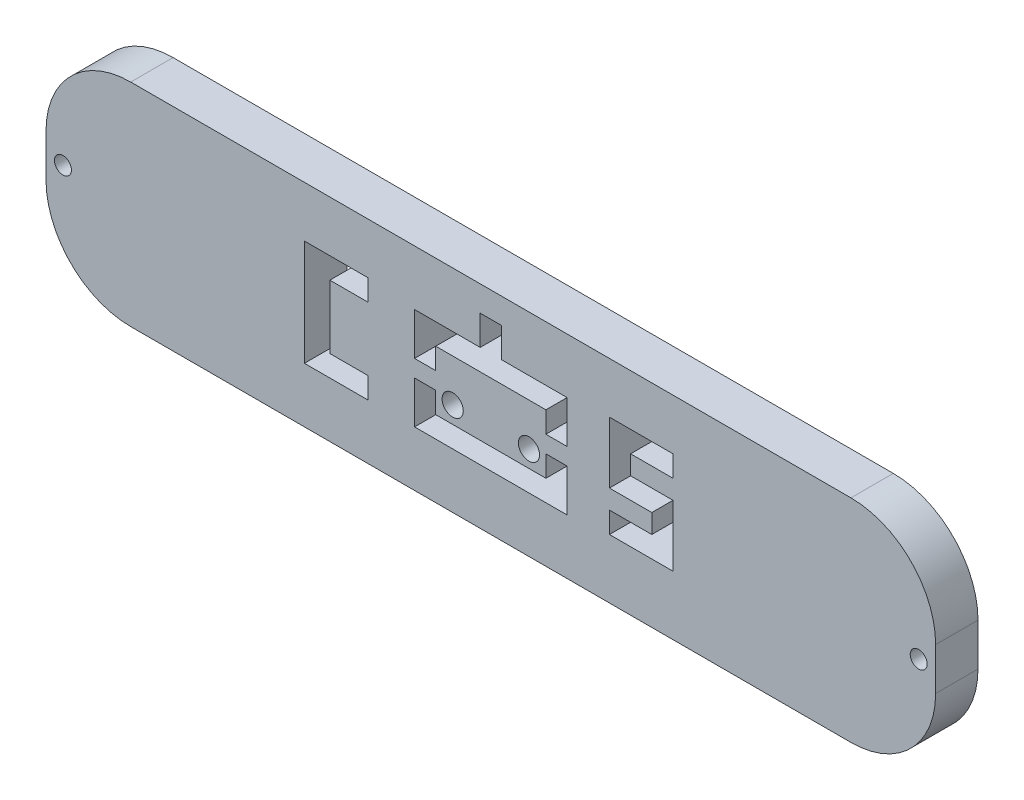
SolidWorks part; units mm, degrees
ref_plane "Alzado" through (0, 0, 0) normal (0, 0, 1) x (1, 0, 0)
ref_plane "Planta" through (0, 0, 0) normal (0, 1, 0) x (1, 0, 0)
ref_plane "Vista lateral" through (0, 0, 0) normal (1, 0, 0) x (0, 0, -1)
sketch "Croquis1" plane through (0, 0, 0) normal (0, 0, 1) x (1, 0, 0)
  line L0 (105, -50) -> (105, 0) construction
  line L1 (0, 0) -> (210, 0)
  line L2 (0, 0) -> (0, -50)
  line L3 (0, -50) -> (210, -50)
  line L4 (210, 0) -> (210, -50)
  line L5 (97.2718, -25) -> (112.9329, -25) construction
  line L6 (87, -13) -> (92, -13)
  line L7 (87, -13) -> (87, -23)
  line L8 (87, -23) -> (92, -23)
  line L9 (92, -13) -> (92, -23)
  line L10 (87, -13) -> (123, -13)
  line L11 (87, -13) -> (87, -18)
  line L12 (87, -18) -> (123, -18)
  line L13 (123, -13) -> (123, -18)
  line L14 (123, -13) -> (118, -13)
  line L15 (123, -13) -> (123, -23)
  line L16 (123, -23) -> (118, -23)
  line L17 (118, -13) -> (118, -23)
  line L18 (123, -27) -> (118, -27)
  line L19 (123, -37) -> (123, -27)
  line L20 (118, -37) -> (118, -27)
  line L21 (87, -37) -> (123, -37)
  line L22 (87, -32) -> (123, -32)
  line L23 (87, -37) -> (87, -27)
  line L24 (87, -27) -> (92, -27)
  line L25 (92, -37) -> (92, -27)
  line L27 (102.5, -6) -> (107.5, -6)
  line L28 (102.5, -6) -> (102.5, -18)
  line L29 (102.5, -18) -> (107.5, -18)
  line L30 (107.5, -6) -> (107.5, -18)
  line L31 (76, -12) -> (61, -12)
  line L32 (76, -12) -> (76, -17)
  line L33 (76, -17) -> (61, -17)
  line L34 (61, -12) -> (61, -17)
  line L35 (61, -12) -> (67, -12)
  line L36 (61, -12) -> (61, -37)
  line L37 (61, -37) -> (67, -37)
  line L38 (67, -12) -> (67, -37)
  line L39 (61, -37) -> (76, -37)
  line L40 (61, -37) -> (61, -32)
  line L41 (61, -32) -> (76, -32)
  line L42 (76, -37) -> (76, -32)
  line L43 (148, -12) -> (133, -12)
  line L44 (148, -12) -> (148, -17)
  line L45 (148, -17) -> (133, -17)
  line L46 (133, -12) -> (133, -17)
  line L47 (133, -12) -> (138, -12)
  line L48 (133, -12) -> (133, -26.5)
  line L49 (133, -26.5) -> (138, -26.5)
  line L50 (138, -12) -> (138, -26.5)
  line L51 (133, -26.5) -> (148, -26.5)
  line L52 (133, -26.5) -> (133, -21.5)
  line L53 (133, -21.5) -> (148, -21.5)
  line L54 (148, -26.5) -> (148, -21.5)
  line L55 (148, -21.5) -> (143, -21.5)
  line L56 (148, -21.5) -> (148, -31)
  line L57 (148, -31) -> (143, -31)
  line L58 (143, -21.5) -> (143, -31)
  line L59 (148, -31) -> (133, -31)
  line L60 (148, -31) -> (148, -36)
  line L61 (148, -36) -> (133, -36)
  line L62 (133, -31) -> (133, -36)
  circle A0 centre (4, -25) radius 2
  circle A1 centre (206, -25) radius 2
  circle A2 centre (96, -28) radius 2.5
  circle A3 centre (114, -28) radius 2.5
  dimension "D3" = 4
  dimension "D4" = 101
  dimension "D5" = 25
  dimension "D6" = 4
  dimension "D7" = 25
  dimension "D8" = 101
  dimension "D17" = 5
  dimension "D18" = 4
  dimension "D19" = 4
  dimension "D20" = 5
  dimension "D21" = 4
  dimension "D22" = 4
  dimension "D45" = 25
  dimension "D30" = 20
  dimension "D31" = 15
  dimension "D32" = 15
  dimension "D33" = 5
  dimension "D34" = 15
  dimension "D35" = 5
  dimension "D1" = 210
  dimension "D2" = 50
  dimension "D9" = 13
  dimension "D10" = 5
  dimension "D11" = 10
  dimension "D12" = 13
  dimension "D13" = 5
  dimension "D14" = 5
  dimension "D15" = 13
  dimension "D16" = 10
  dimension "D23" = 2.5
  dimension "D24" = 2.5
  dimension "D25" = 12
  dimension "D26" = 5
  dimension "D27" = 5
  dimension "D28" = 6
  dimension "D29" = 12
  dimension "D36" = 5
  dimension "D37" = 5
  dimension "D38" = 5
  dimension "D39" = 4.5
  dimension "D40" = 4.5
  dimension "D41" = 20
  dimension "D42" = 25
  dimension "D43" = 15
extrude "Saliente-Extruir1" add sketch "Croquis1" along normal blind 10 contours L1 L30 L10 L13 L15 L16 L17 L12 L9 L8 L7 L6 L28 L2 L3 L4 A3 A2 A1 A0 L25 L22 L20 L18 L19 L21 L23 L24 region at (104.9555, -25.0864, 0)
fillet "Redondeo1" radius 20 4 edges at (210, 0, 5) (210, -50, 5) (0, -50, 5) (0, 0, 5)
